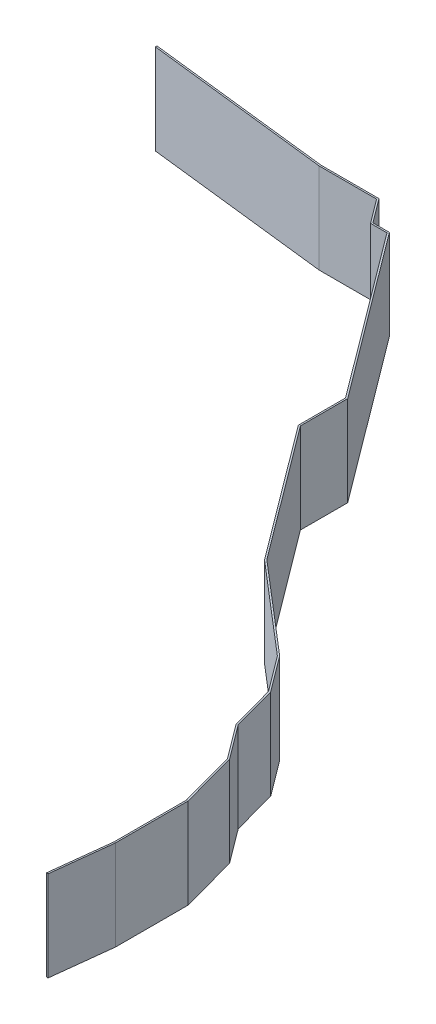
SolidWorks part; units mm, degrees
ref_plane "Front Plane" through (0, 0, 0) normal (0, 0, 1) x (1, 0, 0)
ref_plane "Top Plane" through (0, 0, 0) normal (0, 1, 0) x (1, 0, 0)
ref_plane "Right Plane" through (0, 0, 0) normal (1, 0, 0) x (0, 0, -1)
sketch "Sketch1" plane through (0, 0, 0) normal (0, 1, 0) x (1, 0, 0)
  line L0 (-604.7688, 539.536) -> (-738.9054, -628.864)
  line L1 (-738.9054, -628.864) -> (429.4946, -763.0006)
  line L2 (-604.7688, 539.536) -> (-504.2222, 493.9904)
  line L3 (-504.2222, 493.9904) -> (-420.5407, 493.9904)
  line L4 (-420.5407, 493.9904) -> (-363.6612, 469.8565)
  line L5 (-363.6612, 469.8565) -> (-311.3825, 447.6748)
  line L6 (-311.3825, 447.6748) -> (-262.0693, 381.6508)
  line L7 (-262.0693, 381.6508) -> (-216.8206, 321.0686)
  line L8 (-216.8206, 321.0686) -> (-174.259, 224.4291)
  line L9 (-174.259, 224.4291) -> (-95.8604, 119.4635)
  line L10 (-95.8604, 119.4635) -> (-43.4282, 49.2634)
  line L11 (-43.4282, 49.2634) -> (0, -49.3437)
  line L12 (0, -49.3437) -> (68.7627, -78.5195)
  line L13 (68.7627, -78.5195) -> (156.5417, -196.0443)
  line L14 (156.5417, -196.0443) -> (252.0776, -277.9161)
  line L15 (252.0776, -277.9161) -> (312.2937, -414.6416)
  line L16 (312.2937, -414.6416) -> (392.8261, -522.4641)
  line L17 (392.8261, -522.4641) -> (392.8261, -628.864)
  line L18 (392.8261, -628.864) -> (429.4946, -763.0006)
  line L19 (429.4946, -763.0006) -> (282.1856, -746.089)
  line L20 (282.1856, -746.089) -> (282.1856, -628.864)
  line L21 (282.1856, -628.864) -> (257.7249, -539.3849)
  line L22 (257.7249, -539.3849) -> (217.4587, -485.4736)
  line L23 (217.4587, -485.4736) -> (198.0956, -414.6416)
  line L24 (198.0956, -414.6416) -> (156.5417, -359.0064)
  line L25 (156.5417, -359.0064) -> (68.7627, -283.782)
  line L26 (68.7627, -283.782) -> (14.1499, -236.9802)
  line L27 (14.1499, -236.9802) -> (-45.6453, -156.9221)
  line L28 (-45.6453, -156.9221) -> (-95.8604, -89.6906)
  line L29 (-95.8604, -89.6906) -> (-143.7049, -25.633)
  line L30 (-143.7049, -25.633) -> (-143.7049, 49.2634)
  line L31 (-143.7049, 49.2634) -> (-195.5398, 118.6637)
  line L32 (-195.5398, 118.6637) -> (-262.0693, 207.7381)
  line L33 (-262.0693, 207.7381) -> (-337.5219, 308.7594)
  line L34 (-337.5219, 308.7594) -> (-363.6612, 308.7594)
  line L35 (-363.6612, 308.7594) -> (-392.1009, 346.8365)
  line L36 (-392.1009, 346.8365) -> (-482.9777, 346.8365)
  line L37 (-482.9777, 346.8365) -> (-563.4088, 356.0703)
  line L38 (-563.4088, 356.0703) -> (-625.0193, 363.1434)
  line L39 (-625.0193, 363.1434) -> (-604.7688, 539.536)
  dimension "D1" = 1168.4
  dimension "D2" = 1168.4
extrude "Extrude-Thin1" add sketch "Sketch1" against normal blind 143.002 thin contours L19 L20 L21 L22 L23 L24 L25 L26 L27 L28 L29 L30 L31 L32 L33 L34 L35 L36 L37 L38 L39 thin type one direction wall 2.54
sketch "Sketch2" plane through (-80.8687, 0, 704.409) normal (-0.1141, 0, 0.9935) x (0.9935, 0, 0.1141)
  line L1 (259.0414, 78.7188) -> (612.5182, 78.7188)
  line L2 (259.0414, 78.7188) -> (259.0414, -208.5293)
  line L3 (259.0414, -208.5293) -> (612.5182, -208.5293)
  line L4 (612.5182, 78.7188) -> (612.5182, -208.5293)
extrude "Cut-Extrude1" cut sketch "Sketch2" against normal blind 2.54
sketch "Sketch5" plane through (-80.579, 0, 701.8856) normal (-0.1141, 0, 0.9935) x (0.9935, 0, 0.1141)
  line L0 (367.7041, 0) -> (365.1474, 0) construction
  line L1 (365.1474, 0) -> (367.7041, 0)
  line L2 (365.1474, 0) -> (365.1474, -143.002)
  line L3 (365.1474, -143.002) -> (367.7041, -143.002)
  line L4 (367.7041, 0) -> (367.7041, -143.002)
extrude "Boss-Extrude1" add sketch "Sketch5" along normal blind 96.52
sketch "Sketch6" plane through (-658.0367, 0, -75.545) normal (-0.9935, 0, -0.1141) x (-0.1141, 0, 0.9935)
  line L1 (-576.4113, -289.3886) -> (-140.2042, -289.3886)
  line L2 (-576.4113, -289.3886) -> (-576.4113, 122.0269)
  line L3 (-576.4113, 122.0269) -> (-140.2042, 122.0269)
  line L4 (-140.2042, -289.3886) -> (-140.2042, 122.0269)
extrude "Cut-Extrude3" cut sketch "Sketch6" against normal blind 2.54 contours L2 L3 L4 L1
sketch "Sketch9" plane through (-655.5133, 0, -75.2553) normal (-0.9935, 0, -0.1141) x (-0.1141, 0, 0.9935)
  line L1 (-292.0275, -143.002) -> (-289.4875, -143.002)
  line L2 (-292.0275, -143.002) -> (-292.0275, 0)
  line L3 (-292.0275, 0) -> (-289.4875, 0)
  line L4 (-289.4875, -143.002) -> (-289.4875, 0)
extrude "Boss-Extrude2" add sketch "Sketch9" along normal blind 154.94
